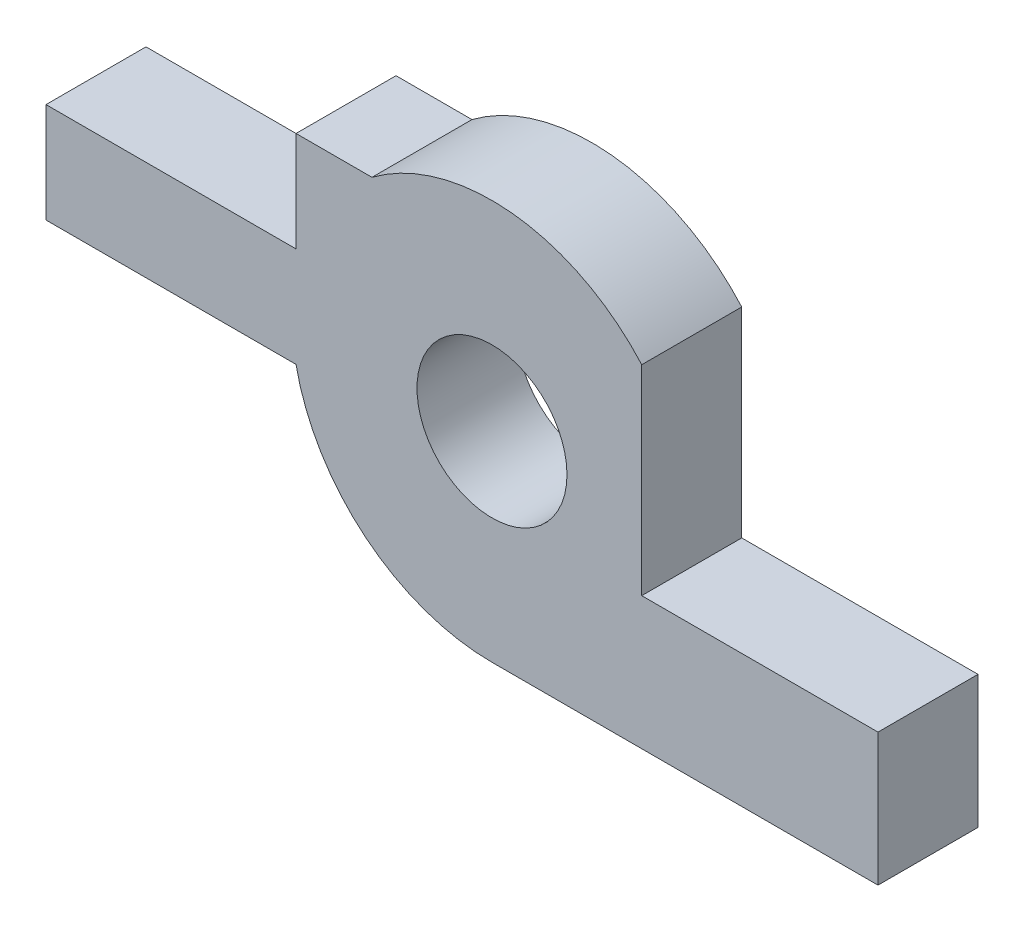
SolidWorks part; units mm, degrees
ref_plane "Front Plane" through (0, 0, 0) normal (0, 0, 1) x (1, 0, 0)
ref_plane "Top Plane" through (0, 0, 0) normal (0, 1, 0) x (1, 0, 0)
ref_plane "Right Plane" through (0, 0, 0) normal (1, 0, 0) x (0, 0, -1)
sketch "Sketch1" plane through (0, 0, 0) normal (0, 0, 1) x (1, 0, 0)
  line L0 (7.72, -4) -> (0, -4)
  line L1 (-3.9192, 1.2) -> (-3.9192, 3.2)
  line L2 (7.72, -1.3485) -> (7.72, -4)
  line L3 (-3.9192, -0.8) -> (-8.9192, -0.8)
  line L4 (2.9949, 2.6515) -> (2.9949, -1.3485)
  line L5 (-8.9192, 1.2) -> (-8.9192, -0.8)
  line L6 (2.9949, -1.3485) -> (7.72, -1.3485)
  line L7 (-3.9192, 1.2) -> (-8.9192, 1.2)
  line L11 (-3.9192, 3.2) -> (-2.4, 3.2)
  circle A0 centre (0, 0) radius 1.5
  arc A1 (2.9949, 2.6515) -> (-2.4, 3.2) centre (0, 0) ccw
  arc A3 (-3.9192, -0.8) -> (0, -4) centre (0, 0) ccw
  dimension "D1" = 2
  dimension "D2" = 3
  dimension "D4" = 4
  dimension "D3" = 7.72
  dimension "D5" = 4
  dimension "D6" = 2.6515
  dimension "D7" = 5
  dimension "D8" = 2
extrude "Boss-Extrude1" add sketch "Sketch1" along normal blind 2
